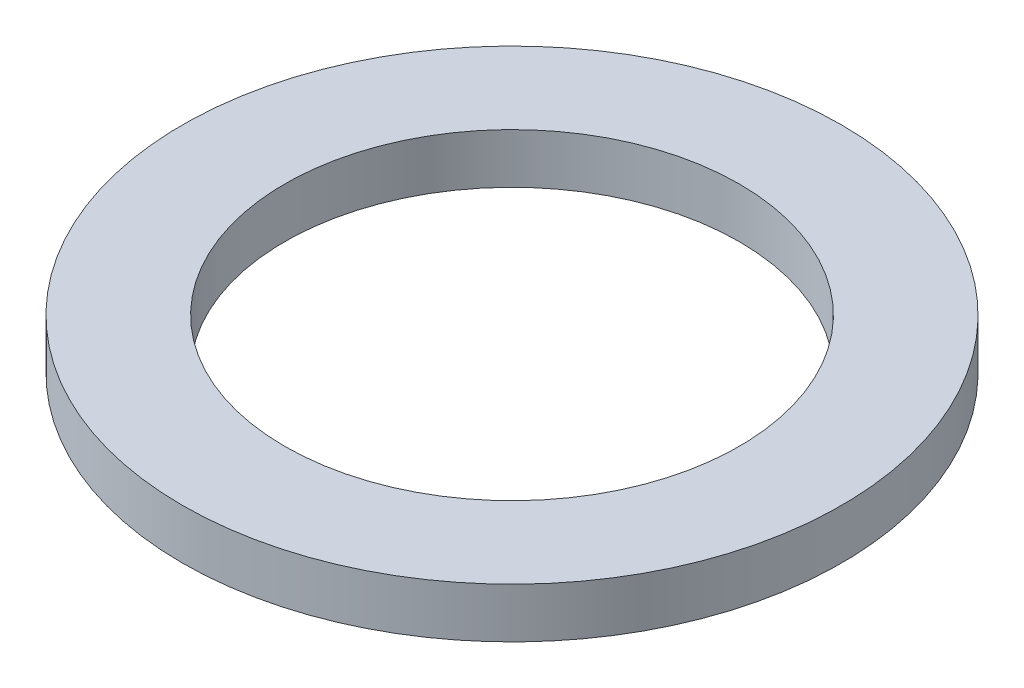
SolidWorks part; units mm, degrees
ref_plane "Front Plane" through (0, 0, 0) normal (0, 0, 1) x (1, 0, 0)
ref_plane "Top Plane" through (0, 0, 0) normal (0, 1, 0) x (1, 0, 0)
ref_plane "Right Plane" through (0, 0, 0) normal (1, 0, 0) x (0, 0, -1)
sketch "Sketch1" plane through (0, 0, 0) normal (0, 1, 0) x (1, 0, 0)
  circle A0 centre (0, 0) radius 72.5
  dimension "FLANGE_OD" = 145
extrude "Boss-Extrude1" add sketch "Sketch1" along normal blind 11
sketch "Sketch2" plane through (0, 0, 0) normal (0, 1, 0) x (1, 0, 0)
  circle A0 centre (0, 0) radius 50
  dimension "BORE_D" = 100
extrude "Cut-Extrude1" cut sketch "Sketch2" along normal through all
sketch "Sketch3" plane through (0, 11, 0) normal (0, 1, 0) x (1, 0, 0)
  circle A0 centre (0, 0) radius 28.7126 construction
  circle A1 centre (-28.7126, 0) radius 2.4493
  dimension "BOLT_D" = 4.8987
  dimension "BOLT_PCD" = 57.4252
extrude "Cut-Extrude2" cut sketch "Sketch3" against normal blind 9.7096 rebuild error yes
pattern_circular "CirPattern1" count 3 over 360 rebuild error yes
